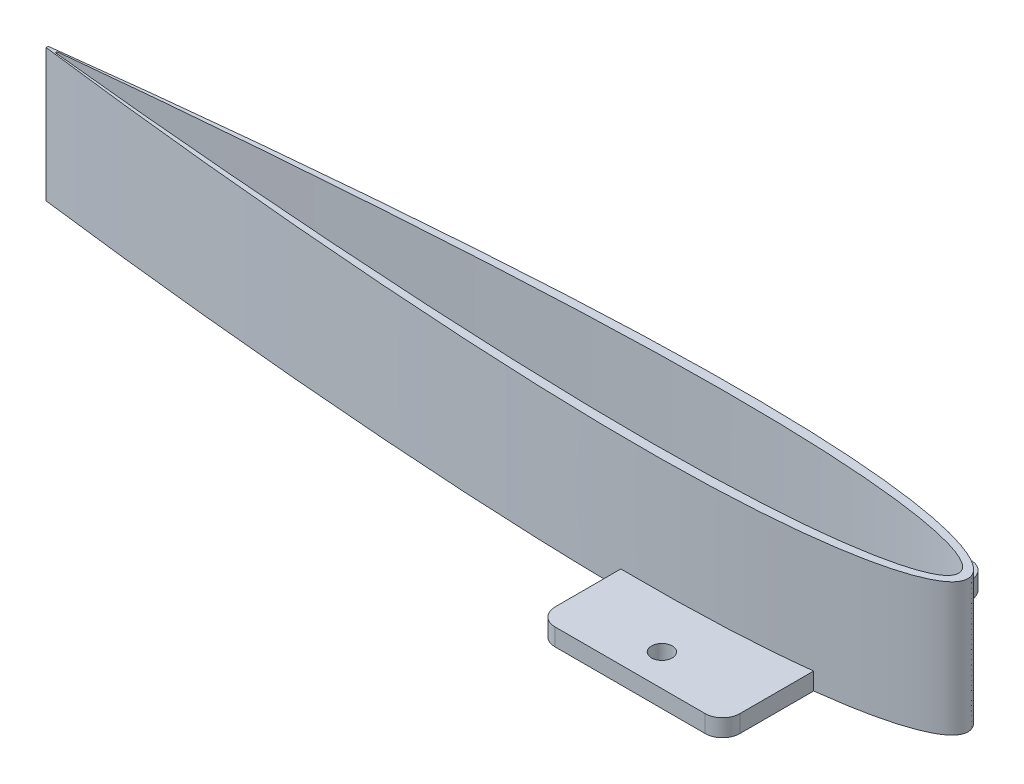
SolidWorks part; units mm, degrees
ref_plane "Front Plane" through (0, 0, 0) normal (0, 0, 1) x (1, 0, 0)
ref_plane "Top Plane" through (0, 0, 0) normal (0, 1, 0) x (1, 0, 0)
ref_plane "Right Plane" through (0, 0, 0) normal (1, 0, 0) x (0, 0, -1)
sketch "Sketch1" plane through (0, 0, 0) normal (0, 1, 0) x (1, 0, 0)
  line L0 (-157.869, 0.1813) -> (-157.869, -0.1813)
  spline S0 degree 3 poles (-157.869, 0.1813) (-157.7234, 0.1997) (-157.1427, 0.2731) (-155.842, 0.4363) (-153.6899, 0.7029) (-150.7102, 1.0648) (-146.9353, 1.5117) (-142.4066, 2.0316) (-137.1737, 2.6112) (-131.294, 3.2365) (-124.8318, 3.8933) (-117.858, 4.5667) (-110.449, 5.2418) (-102.686, 5.9027) (-94.654, 6.533) (-86.441, 7.115) (-78.1369, 7.6306) (-69.8327, 8.0607) (-61.6192, 8.3869) (-53.5863, 8.5915) (-45.8219, 8.6593) (-38.411, 8.5785) (-31.4345, 8.3417) (-24.9688, 7.9466) (-19.0842, 7.3966) (-13.8445, 6.7) (-9.305, 5.8706) (-5.5136, 4.924) (-2.4982, 3.8818) (-0.2842, 2.7479) (1.1872, 1.5211) (1.7791, 0) (1.1872, -1.5211) (-0.2842, -2.7479) (-2.4982, -3.8818) (-5.5136, -4.924) (-9.305, -5.8706) (-13.8445, -6.7) (-19.0842, -7.3966) (-24.9688, -7.9466) (-31.4345, -8.3417) (-38.411, -8.5785) (-45.8219, -8.6593) (-53.5863, -8.5915) (-61.6192, -8.3869) (-69.8327, -8.0607) (-78.1369, -7.6306) (-86.441, -7.115) (-94.654, -6.533) (-102.686, -5.9027) (-110.449, -5.2418) (-117.858, -4.5667) (-124.8318, -3.8933) (-131.294, -3.2365) (-137.1737, -2.6112) (-142.4066, -2.0316) (-146.9353, -1.5117) (-150.7102, -1.0648) (-153.6899, -0.7029) (-155.842, -0.4363) (-157.1427, -0.2731) (-157.7234, -0.1997) (-157.869, -0.1813) knots 0 0 0 0 0.001358 0.005418 0.012133 0.021428 0.033199 0.047314 0.063617 0.081926 0.102039 0.123733 0.14677 0.170894 0.195841 0.221335 0.247097 0.272844 0.298294 0.323173 0.347211 0.370154 0.391761 0.41181 0.430099 0.446451 0.460717 0.472784 0.482593 0.49017 0.495736 0.5 0.504264 0.50983 0.517407 0.527216 0.539283 0.553549 0.569901 0.58819 0.608239 0.629846 0.652789 0.676827 0.701706 0.727156 0.752903 0.778665 0.804159 0.829106 0.85323 0.876267 0.897961 0.918074 0.936383 0.952686 0.966801 0.978572 0.987867 0.994582 0.998642 1 1 1 1
extrude "Boss-Extrude1" add sketch "Sketch1" along normal blind 23
sketch "Sketch2" plane through (0, 0, 0) normal (0, 1, 0) x (1, 0, 0)
  line L0 (-46.9, -23) -> (-20.9, -23)
  line L1 (-17.9, -20) -> (-17.9, 20)
  line L2 (-20.9, 23) -> (-46.9, 23)
  line L3 (-49.9, 20) -> (-49.9, -20)
  arc A0 (-20.9, -23) -> (-17.9, -20) centre (-20.9, -20) ccw
  arc A1 (-17.9, 20) -> (-20.9, 23) centre (-20.9, 20) ccw
  arc A2 (-46.9, 23) -> (-49.9, 20) centre (-46.9, 20) ccw
  arc A3 (-49.9, -20) -> (-46.9, -23) centre (-46.9, -20) ccw
extrude "Boss-Extrude2" add sketch "Sketch2" along normal blind 3
ref_plane "Plane1" through (0, 23, 0) normal (0, 1, 0) x (1, 0, 0)
sketch "Sketch3" plane through (0, 23, 0) normal (0, 1, 0) x (1, 0, 0)
  line L0 (-156.269, 0.1477) -> (-156.269, -0.1477)
  spline S0 degree 3 poles (-156.269, 0.1477) (-156.1263, 0.1627) (-155.5572, 0.2225) (-154.2826, 0.3555) (-152.1737, 0.5726) (-149.2537, 0.8674) (-145.5544, 1.2315) (-141.1165, 1.6551) (-135.9886, 2.1272) (-130.2268, 2.6367) (-123.8942, 3.1717) (-117.0603, 3.7203) (-109.8, 4.2702) (-102.1927, 4.8087) (-94.3218, 5.3221) (-86.2736, 5.7963) (-78.1362, 6.2162) (-69.9986, 6.5667) (-61.95, 6.8323) (-54.0786, 6.999) (-46.4703, 7.0543) (-39.2087, 6.9885) (-32.373, 6.7956) (-26.038, 6.4738) (-20.2728, 6.026) (-15.1403, 5.4587) (-10.6947, 4.7843) (-6.9845, 4.0133) (-4.0368, 3.1721) (-1.8833, 2.2485) (-0.4487, 1.2944) (0.1855, 0) (-0.4487, -1.2944) (-1.8833, -2.2485) (-4.0368, -3.1721) (-6.9845, -4.0133) (-10.6947, -4.7843) (-15.1403, -5.4587) (-20.2728, -6.026) (-26.038, -6.4738) (-32.373, -6.7956) (-39.2087, -6.9885) (-46.4703, -7.0543) (-54.0786, -6.999) (-61.95, -6.8323) (-69.9986, -6.5667) (-78.1362, -6.2162) (-86.2736, -5.7963) (-94.3218, -5.3221) (-102.1927, -4.8087) (-109.8, -4.2702) (-117.0603, -3.7203) (-123.8942, -3.1717) (-130.2268, -2.6367) (-135.9886, -2.1272) (-141.1165, -1.6551) (-145.5544, -1.2315) (-149.2537, -0.8674) (-152.1737, -0.5726) (-154.2826, -0.3555) (-155.5572, -0.2225) (-156.1263, -0.1627) (-156.269, -0.1477) knots 0 0 0 0 0.001361 0.005428 0.012156 0.02147 0.033267 0.047415 0.063758 0.082114 0.102282 0.124039 0.147146 0.171348 0.196379 0.221963 0.247821 0.273669 0.299223 0.324206 0.348349 0.37139 0.393087 0.41321 0.431552 0.447929 0.462182 0.474186 0.48386 0.491199 0.496361 0.5 0.503639 0.508801 0.51614 0.525814 0.537818 0.552071 0.568448 0.58679 0.606913 0.62861 0.651651 0.675794 0.700777 0.726331 0.752179 0.778037 0.803621 0.828652 0.852854 0.875961 0.897718 0.917886 0.936242 0.952585 0.966733 0.97853 0.987844 0.994572 0.998639 1 1 1 1
extrude "Cut-Extrude1" cut sketch "Sketch3" against normal blind 20
sketch "Sketch4" plane through (0, 0, 0) normal (0, 1, 0) x (1, 0, 0)
  circle A0 centre (-33.9, -17.5) radius 1.8
  circle A1 centre (-33.9, 17.5) radius 1.8
extrude "Cut-Extrude2" cut sketch "Sketch4" along normal blind 3
